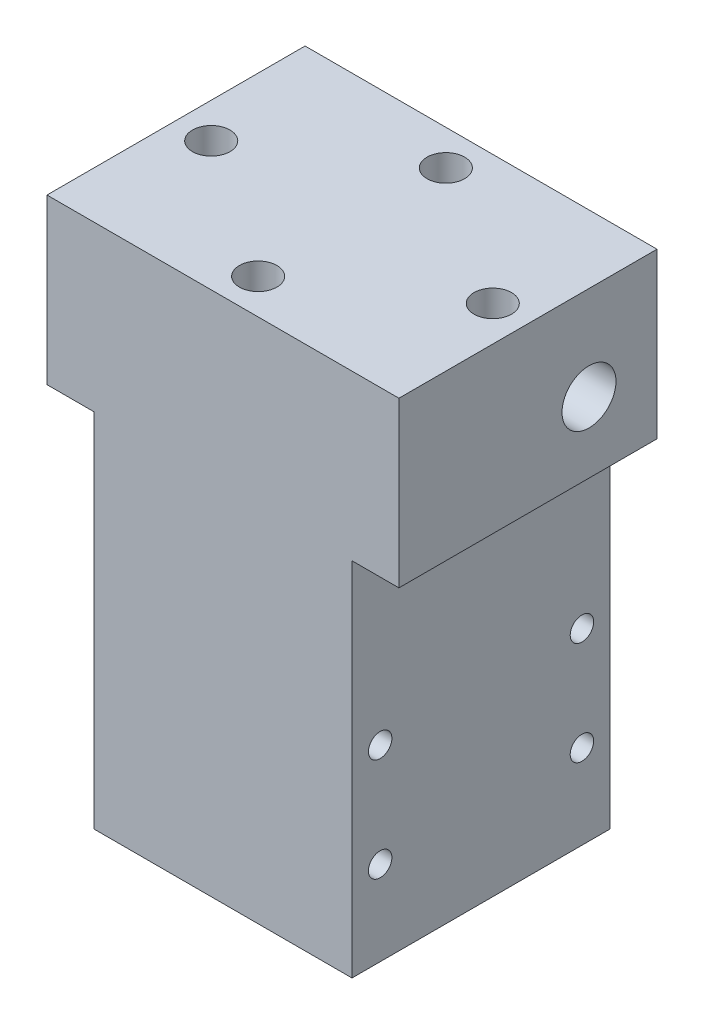
SolidWorks part; units mm, degrees
ref_plane "Alzado" through (0, 0, 0) normal (0, 0, 1) x (1, 0, 0)
ref_plane "Planta" through (0, 0, 0) normal (0, 1, 0) x (1, 0, 0)
ref_plane "Vista lateral" through (0, 0, 0) normal (1, 0, 0) x (0, 0, -1)
sketch "Croquis1" plane through (0, 0, 0) normal (0, 0, 1) x (1, 0, 0)
  line L0 (37.5, 0) -> (-37.5, 0)
  line L1 (-37.5, 0) -> (-37.5, -35)
  line L2 (-37.5, -35) -> (-27.5, -35)
  line L3 (-27.5, -35) -> (-27.5, -112)
  line L4 (-27.5, -112) -> (27.5, -112)
  line L5 (27.5, -112) -> (27.5, -35)
  line L6 (27.5, -35) -> (37.5, -35)
  line L7 (37.5, -35) -> (37.5, 0)
  dimension "D1" = 37.5
  dimension "D2" = 37.5
  dimension "D3" = 27.5
  dimension "D4" = 27.5
  dimension "D5" = 35
  dimension "D6" = 77
  dimension "D7" = 35
extrude "Saliente-Extruir1" add sketch "Croquis1" along normal blind 27.5 and the other way blind 27.5
sketch "Croquis2" plane through (0, 0, 0) normal (0, 1, 0) x (1, 0, 0)
  circle A0 centre (-30, 0) radius 4
  circle A1 centre (0, 20) radius 4
  circle A2 centre (30, 0) radius 4
  circle A3 centre (0, -20) radius 4
  dimension "D5" = 8
  dimension "D6" = 8
  dimension "D7" = 8
  dimension "D8" = 8
  dimension "D1" = 20
  dimension "D2" = 20
  dimension "D3" = 30
  dimension "D4" = 30
extrude "Cortar-Extruir1" cut sketch "Croquis2" against normal blind 30
sketch "Croquis3" plane through (27.5, 0, 0) normal (1, 0, 0) x (0, 0, -1)
  line L0 (27.5, -112) -> (-27.5, -112) construction
  circle A0 centre (-21.5, -94) radius 2.5
  circle A1 centre (-21.5, -72) radius 2.5
  circle A2 centre (21.5, -72) radius 2.5
  circle A3 centre (21.5, -94) radius 2.5
  dimension "D2" = 22
  dimension "D3" = 18
  dimension "D4" = 22
  dimension "D5" = 21.5
  dimension "D6" = 21.5
  dimension "D7" = 21.5
  dimension "D8" = 21.5
  dimension "D9" = 5
  dimension "D10" = 5
  dimension "D11" = 5
  dimension "D12" = 5
  dimension "D1" = 18
extrude "Cortar-Extruir2" cut sketch "Croquis3" against normal blind 22
sketch "Croquis4" plane through (-27.5, 0, 0) normal (-1, 0, 0) x (0, 0, 1)
  line L0 (-27.5, -112) -> (27.5, -112) construction
  circle A0 centre (-21.5, -94) radius 2.5
  circle A1 centre (-21.5, -72) radius 2.5
  circle A2 centre (21.5, -72) radius 2.5
  circle A3 centre (21.5, -94) radius 2.5
  dimension "D2" = 22
  dimension "D3" = 21.5
  dimension "D4" = 21.5
  dimension "D5" = 5
  dimension "D1" = 18
extrude "Cortar-Extruir3" cut sketch "Croquis4" against normal blind 22
sketch "Croquis5" plane through (0, -112, 0) normal (0, -1, 0) x (1, 0, 0)
  circle A0 centre (0, 0) radius 11
  dimension "D1" = 22
extrude "Cortar-Extruir4" cut sketch "Croquis5" against normal blind 2
sketch "Croquis6" plane through (37.5, 0, 0) normal (1, 0, 0) x (0, 0, -1)
  line L0 (27.5, 0) -> (-27.5, 0) construction
  circle A0 centre (13, -20) radius 5.75
  dimension "D1" = 20
  dimension "D2" = 13
  dimension "D3" = 11.5
extrude "Cortar-Extruir5" cut sketch "Croquis6" against normal blind 20
sketch "Croquis7" plane through (-37.5, 0, 0) normal (-1, 0, 0) x (0, 0, 1)
  line L0 (-27.5, 0) -> (27.5, 0) construction
  circle A0 centre (-13, -20) radius 5.75
  dimension "D1" = 20
  dimension "D2" = 13
  dimension "D3" = 11.5
extrude "Cortar-Extruir6" cut sketch "Croquis7" against normal blind 20
sketch "Croquis8" plane through (0, -110, 0) normal (0, -1, 0) x (1, 0, 0)
  circle A0 centre (0, 0) radius 3
  dimension "D1" = 6
extrude "Cortar-Extruir7" cut sketch "Croquis8" against normal blind 30
